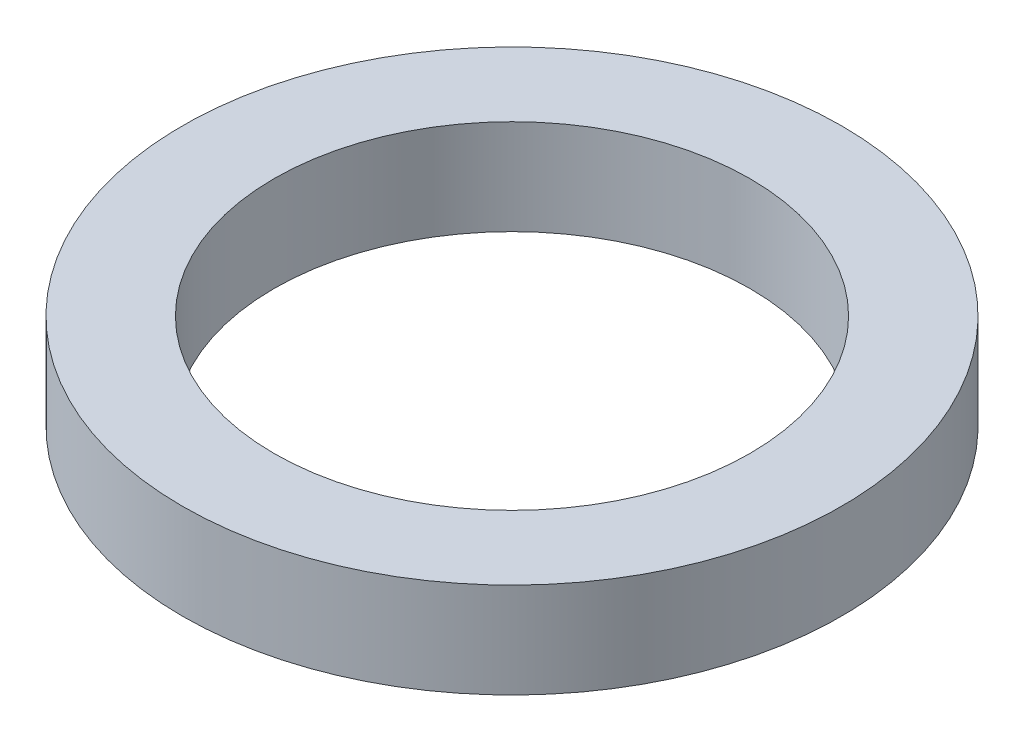
SolidWorks part; units mm, degrees
ref_plane "Front Plane" through (0, 0, 0) normal (0, 0, 1) x (1, 0, 0)
ref_plane "Top Plane" through (0, 0, 0) normal (0, 1, 0) x (1, 0, 0)
ref_plane "Right Plane" through (0, 0, 0) normal (1, 0, 0) x (0, 0, -1)
sketch "Sketch1" plane through (0, 0, 0) normal (0, 1, 0) x (1, 0, 0)
  circle A0 centre (0, 0) radius 45
  dimension "FLANGE_OD" = 90
extrude "Boss-Extrude1" add sketch "Sketch1" along normal blind 13
sketch "Sketch2" plane through (0, 0, 0) normal (0, 1, 0) x (1, 0, 0)
  circle A0 centre (0, 0) radius 32.5
  dimension "BORE_D" = 65
extrude "Cut-Extrude1" cut sketch "Sketch2" along normal through all
sketch "Sketch3" plane through (0, 13, 0) normal (0, 1, 0) x (1, 0, 0)
  circle A0 centre (0, 0) radius 18.2993 construction
  circle A1 centre (-18.2993, 0) radius 1.8339
  dimension "BOLT_D" = 3.6677
  dimension "BOLT_PCD" = 36.5986
extrude "Cut-Extrude2" cut sketch "Sketch3" against normal blind 8.259 rebuild error yes
pattern_circular "CirPattern1" count 8 over 360 rebuild error yes
